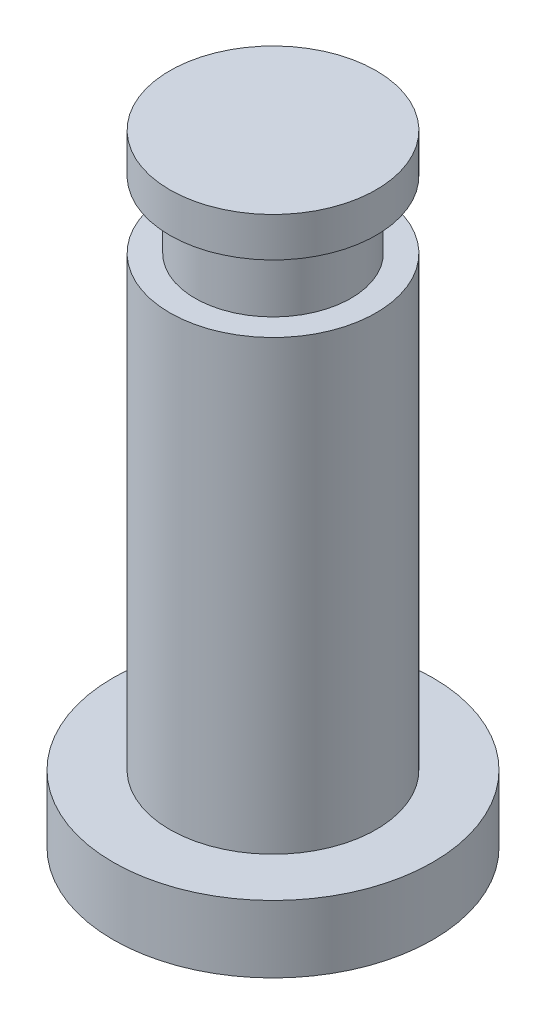
SolidWorks part; units mm, degrees
ref_plane "Front Plane" through (0, 0, 0) normal (0, 0, 1) x (1, 0, 0)
ref_plane "Top Plane" through (0, 0, 0) normal (0, 1, 0) x (1, 0, 0)
ref_plane "Right Plane" through (0, 0, 0) normal (1, 0, 0) x (0, 0, -1)
sketch "Sketch1" plane through (0, 0, 0) normal (0, 1, 0) x (1, 0, 0)
  circle A0 centre (0, 0) radius 6.15
  circle A1 centre (0, 0) radius 9.525
  dimension "D1" = 12.3
  dimension "D2" = 19.05
extrude "Boss-Extrude1" add sketch "Sketch1" along normal blind 33.02 contours A0 region at (0, 0, 0)
extrude "Boss-Extrude2" add sketch "Sketch1<4>" against normal blind 4 contours A0 | A1 A0 region at (0, 0, 0) region at (-9.2556, 0, 0)
sketch "Sketch1<4>" plane through (0, 0, 0) normal (0, 1, 0) x (1, 0, 0) same geometry as "Sketch1"
sketch "Sketch2" plane through (0, 0, 0) normal (0, 0, 1) x (1, 0, 0)
  line L0 (0, -951.607) -> (0, 49048.393) construction
  line L1 (6.15, 30.67) -> (4.65, 30.67)
  line L2 (6.15, 30.67) -> (6.15, 26.67)
  line L3 (6.15, 26.67) -> (4.65, 26.67)
  line L4 (4.65, 30.67) -> (4.65, 26.67)
  line L5 (6.15, 0) -> (6.15, 33.02) construction
  line L6 (9.525, 0) -> (-9.525, 0) construction
  dimension "D1" = 1.5
  dimension "D2" = 4
  dimension "D3" = 26.67
revolve "Cut-Revolve1" cut sketch "Sketch2" angle 360 about L0
